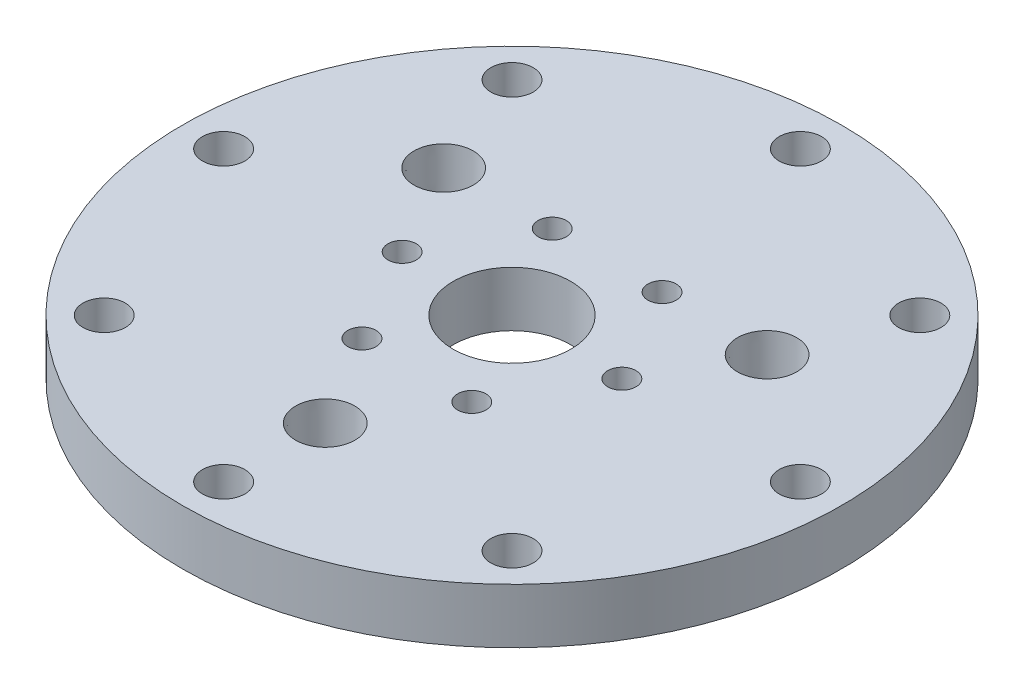
SolidWorks part; units mm, degrees
material "AISI Type 316L stainless steel"
ref_plane "Front Plane" through (0, 0, 0) normal (0, 0, 1) x (1, 0, 0)
ref_plane "Top Plane" through (0, 0, 0) normal (0, 1, 0) x (1, 0, 0)
ref_plane "Right Plane" through (0, 0, 0) normal (1, 0, 0) x (0, 0, -1)
sketch "Sketch1" plane through (0, 0, 0) normal (0, 1, 0) x (1, 0, 0)
  circle A0 centre (0, 0) radius 76.2
  dimension "D1" = 152.4
extrude "Boss-Extrude1" add sketch "Sketch1" along normal blind 12.7
hole_wizard "3/8 Clearance Hole1" positions "Sketch2" profile "Sketch3" hole size "3/8" standard "ANSI Inch" end condition through all
sketch "Sketch2" plane through (0, 12.7, 0) normal (0, 1, 0) x (1, 0, 0)
  line L1 (66.675, 0) -> (47.1463, 47.1463)
  line L2 (47.1463, 47.1463) -> (0, 66.675)
  line L3 (0, 66.675) -> (-47.1463, 47.1463)
  line L4 (-47.1463, 47.1463) -> (-66.675, 0)
  line L5 (-66.675, 0) -> (-47.1463, -47.1463)
  line L6 (-47.1463, -47.1463) -> (0, -66.675)
  line L7 (0, -66.675) -> (47.1463, -47.1463)
  line L8 (47.1463, -47.1463) -> (66.675, 0)
  line L9 (0, 0) -> (66.675, 0) construction
  circle A0 centre (0, 0) radius 66.675 construction
  point P3 (66.675, 0)
  point P4 (47.1463, 47.1463)
  point P5 (0, 66.675)
  point P6 (-47.1463, 47.1463)
  point P7 (-66.675, 0)
  point P8 (-47.1463, -47.1463)
  point P9 (0, -66.675)
  point P10 (47.1463, -47.1463)
  dimension "D1" = 133.35
sketch "Sketch3" plane through (47.1463, 12.7, 47.1463) normal (1, 0, 0) x (0, 0, 1)
  line L0 (0, 0) -> (0, 12.7)
  line L1 (0, 12.7) -> (4.9022, 12.7)
  line L2 (4.9022, 12.7) -> (4.9022, 0)
  line L5 (4.9022, 0) -> (0, 0)
  line L11 (0, -6.35) -> (0, 107.95) construction
  dimension "Thru Hole Dia." = 9.8044
  dimension "Thru Hole Depth" = 12.7
hole_wizard "1/4 Clearance Hole1" positions "Sketch4" profile "Sketch5" hole size "1/4" standard "ANSI Inch" end condition through all
sketch "Sketch4" plane through (0, 12.7, 0) normal (0, 1, 0) x (1, 0, 0)
  line L2 (25.4, 0) -> (12.7, 21.997)
  line L3 (12.7, 21.997) -> (-12.7, 21.997)
  line L4 (-12.7, 21.997) -> (-25.4, 0)
  line L5 (-25.4, 0) -> (-12.7, -21.997)
  line L6 (-12.7, -21.997) -> (12.7, -21.997)
  line L7 (12.7, -21.997) -> (25.4, 0)
  circle A0 centre (0, 0) radius 25.4 construction
  point P5 (25.4, 0)
  point P6 (12.7, 21.997)
  point P7 (-12.7, 21.997)
  point P8 (-25.4, 0)
  point P9 (-12.7, -21.997)
  point P10 (12.7, -21.997)
  dimension "D1" = 50.8
sketch "Sketch5" plane through (12.7, 12.7, 21.997) normal (1, 0, 0) x (0, 0, 1)
  line L0 (0, 0) -> (0, 12.7)
  line L1 (0, 12.7) -> (3.2639, 12.7)
  line L2 (3.2639, 12.7) -> (3.2639, 0)
  line L5 (3.2639, 0) -> (0, 0)
  line L11 (0, -6.35) -> (0, 107.95) construction
  dimension "Thru Hole Dia." = 6.5278
  dimension "Thru Hole Depth" = 12.7
hole_wizard "1/4 NPT Tapped Hole1" positions "Sketch6" profile "Sketch7" size "1/4" standard "ANSI Inch" end condition through all
sketch "Sketch6" plane through (0, 12.7, 0) normal (0, 1, 0) x (1, 0, 0)
  line L1 (0, -43.18) -> (37.395, 21.59)
  line L2 (37.395, 21.59) -> (-37.395, 21.59)
  line L3 (-37.395, 21.59) -> (0, -43.18)
  line L4 (0, 0) -> (0, -43.18) construction
  circle A0 centre (0, 0) radius 43.18 construction
  point P3 (0, -43.18)
  point P4 (37.395, 21.59)
  point P5 (-37.395, 21.59)
  dimension "D1" = 43.18
sketch "Sketch7" plane through (-37.395, 12.7, -21.59) normal (1, 0, 0) x (0, 0, 1)
  line L0 (0, 0) -> (0, 12.7)
  line L1 (0, 12.7) -> (5.5626, 12.7)
  line L2 (-6.558, 9.906) -> (-6.8546, 0) construction
  line L3 (5.5626, 12.7) -> (5.5626, 9.906)
  line L4 (5.5626, 9.906) -> (6.558, 9.906)
  line L5 (6.558, 9.906) -> (6.8546, 0)
  line L7 (6.8546, 0) -> (0, 0)
  line L8 (0, -6.35) -> (0, 107.95) construction
  line L11 (-5.5626, 9.906) -> (-6.558, 9.906) construction
  dimension "Thru Tap Drill Dia." = 11.1252
  dimension "Thru Tap Drill Depth" = 12.7
  dimension "Thread Dia." = 13.7092
  dimension "Thread Angle" = 3.43
  dimension "Thread Depth" = 9.906
sketch "Sketch8" plane through (0, 12.7, 0) normal (0, 1, 0) x (1, 0, 0)
  circle A0 centre (0, 0) radius 13.6
  dimension "D1" = 27.2
extrude "Cut-Extrude1" cut sketch "Sketch8" against normal through all
chamfer "Chamfer1" [suppressed] distance 3.175 angle 45
